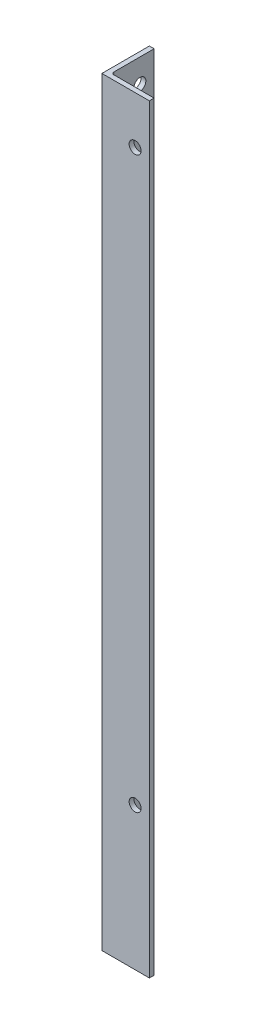
SolidWorks part; units mm, degrees
ref_plane "Front Plane" through (0, 0, 0) normal (0, 0, 1) x (1, 0, 0)
ref_plane "Top Plane" through (0, 0, 0) normal (0, 1, 0) x (1, 0, 0)
ref_plane "Right Plane" through (0, 0, 0) normal (1, 0, 0) x (0, 0, -1)
sketch "Sketch2" plane through (0, 0, 0) normal (0, 1, 0) x (1, 0, 0)
  line L0 (0, 31.75) -> (3.175, 31.75)
  line L1 (3.175, 31.75) -> (3.175, 4.7625)
  line L2 (4.7625, 3.175) -> (31.75, 3.175)
  line L3 (31.75, 3.175) -> (31.75, 0)
  line L4 (31.75, 0) -> (0, 0)
  line L5 (0, 0) -> (0, 31.75)
  arc A0 (3.175, 4.7625) -> (4.7625, 3.175) centre (4.7625, 4.7625) ccw
  point P9 (1.5875, 31.75)
  point P10 (31.75, 1.5875)
  dimension "D5" = 3.175
  dimension "D1" = 31.75
  dimension "D2" = 31.75
  dimension "D3" = 3.175
  dimension "D4" = 3.175
extrude "Boss-Extrude1" add sketch "Sketch2" along normal blind 508
sketch "LeftSideHoles-Sketch3" plane through (0, 0, 0) normal (0, 0, 1) x (1, 0, 0)
  line L0 (0, 0) -> (31.75, 0) construction
  line L1 (0, 508) -> (31.75, 508) construction
  line L3 (0, 508) -> (0, 0) construction
  circle A0 centre (22.225, 95.4) radius 4
  circle A6 centre (22.225, 476.25) radius 4
  dimension "D3" = 8
  dimension "D1" = 95.4
  dimension "D2" = 22.225
  dimension "D8" = 31.75
  dimension "D4" = 476.25
sketch "BackSideHoles-Sketch4" plane through (0, 0, 0) normal (-1, 0, 0) x (0, 0, 1)
  line L0 (-31.75, 508) -> (0, 508) construction
  line L1 (0, 508) -> (0, 0) construction
  line L3 (-31.75, 0) -> (0, 0) construction
  circle A0 centre (-22.225, 95.4) radius 4
  circle A5 centre (-22.225, 492.125) radius 4
  circle A11 centre (-22.225, 351.5849) radius 4
  dimension "D2" = 22.225
  dimension "D4" = 8
  dimension "D1" = 351.5849
  dimension "D3" = 95.4
  dimension "D5" = 15.875
extrude "BackSideHoles-Cut-Extrude1" cut sketch "LeftSideHoles-Sketch3" against normal blind 3.175
extrude "RightSideHoles-Cut-Extrude2" cut sketch "BackSideHoles-Sketch4" against normal blind 3.175
equation "\"RailThickness\"= .125in'Spec"
equation "\"VSWidth\"= 1.25in'Spec"
equation "\"VSHeight\"= 1.25in'Spec"
equation "\"VSLength\"= 20.0in"
equation "\"VSBottomSideRailHoleYFromBottomOfLowerRailYSValue\"= 95.4mm"
equation "\"FasteningHoleDiameter\"= .125in"
equation "\"VSTopSideRailHoleYFromEdge\"= \"TopRailHeight\" / 2"
equation "\"D1@LeftSideHoles-Sketch3\"=\"VSBottomSideRailHoleYFromBottomOfLowerRailYSValue\""
equation "\"D2@LeftSideHoles-Sketch3\"=\"FrameFastenerHoleOffsetFromSide\""
equation "\"D1@Boss-Extrude1\"=\"VSLength\""
equation "\"D4@BackSideHoles-Sketch4\"=\"FrameFastenerHoleDiameter\""
equation "\"VSMidSideRailHoleYFromV8TopOfMidSideRailYSValue\"= 351.58487mm"
equation "\"D1@Sketch2\"=\"VSHeight\""
equation "\"D2@Sketch2\"=\"VSWidth\""
equation "\"TopRailHeight\"= 1.25in"
equation "\"V1 BottomOfLowerRail\"= \"LegHeight\""
equation "\"D1@BackSideHoles-Sketch4\"=\"VSMidSideRailHoleYFromV8TopOfMidSideRailYSValue\""
equation "\"D3@BackSideHoles-Sketch4\"=\"VSBottomSideRailHoleYFromBottomOfLowerRailYSValue\""
equation "\"D8@LeftSideHoles-Sketch3\"=\"TopBackRailHeight\" / 2"
equation "\"D5@Sketch2\"=\"FasteningHoleDiameter\""
equation "\"FrameFastenerHoleDiameter\"= 8mm"
equation "\"FrameFastenerHoleOffsetFromSide\"= \"VSWidth\" / 2 + \"GapBetweenVerticalSupportsAndRails\""
equation "\"D2@BackSideHoles-Sketch4\"=\"FrameFastenerHoleOffsetFromSide\""
equation "\"D3@LeftSideHoles-Sketch3\"=\"FrameFastenerHoleDiameter\""
equation "\"D5@BackSideHoles-Sketch4\"=\"VSTopSideRailHoleYFromEdge\""
equation "\"TopBackRailHeight\"= 2.5in"
equation "\"GapBetweenVerticalSupportsAndRails\"= \"RailThickness\" * 2"
